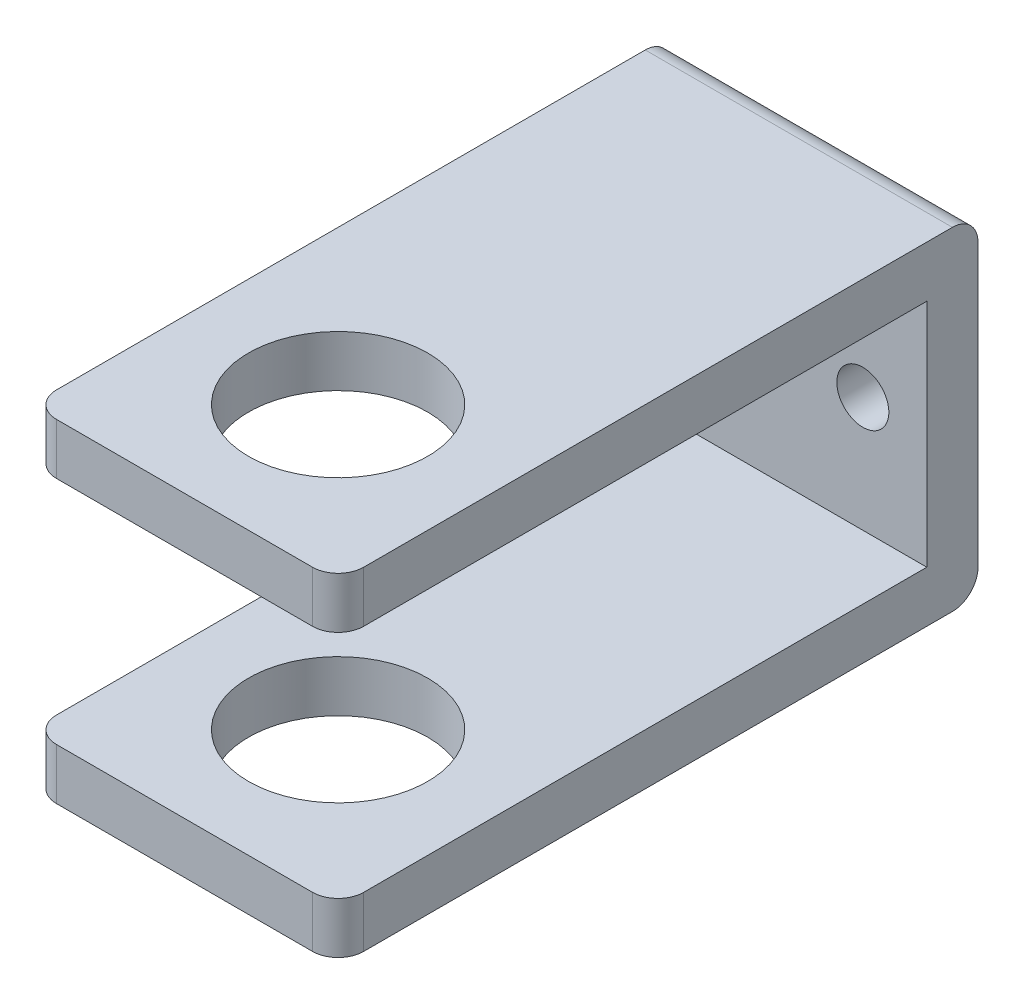
SolidWorks part; units mm, degrees
ref_plane "Front Plane" through (0, 0, 0) normal (0, 0, 1) x (1, 0, 0)
ref_plane "Top Plane" through (0, 0, 0) normal (0, 1, 0) x (1, 0, 0)
ref_plane "Right Plane" through (0, 0, 0) normal (1, 0, 0) x (0, 0, -1)
sketch "Sketch1" plane through (0, 0, 0) normal (0, 1, 0) x (1, 0, 0)
  line L1 (-19.05, -39.6875) -> (19.05, -39.6875)
  line L2 (-19.05, -39.6875) -> (-19.05, 39.6875)
  line L3 (-19.05, 39.6875) -> (19.05, 39.6875)
  line L4 (19.05, -39.6875) -> (19.05, 39.6875)
  line L5 (-19.05, -39.6875) -> (19.05, 39.6875) construction
  line L6 (-19.05, 39.6875) -> (19.05, -39.6875) construction
  point P0 (0, 0)
  dimension "D1" = 38.1
  dimension "D2" = 79.375
extrude "Boss-Extrude1" add sketch "Sketch1" along normal blind 41.275
sketch "Sketch2" plane through (0, 0, 39.6875) normal (0, 0, 1) x (1, 0, 0)
  line L0 (-19.05, 41.275) -> (-19.05, 0) construction
  line L1 (-19.05, 34.925) -> (19.05, 34.925)
  line L2 (-19.05, 34.925) -> (-19.05, 6.35)
  line L3 (-19.05, 6.35) -> (19.05, 6.35)
  line L4 (19.05, 34.925) -> (19.05, 6.35)
  line L5 (19.05, 41.275) -> (19.05, 0) construction
  line L6 (-19.05, 41.275) -> (19.05, 41.275) construction
  line L7 (-19.05, 0) -> (19.05, 0) construction
  dimension "D1" = 6.35
  dimension "D2" = 6.35
extrude "Cut-Extrude1" cut sketch "Sketch2" against normal offset from surface (73.025 mm away) 6.35 up to face at (0, 20.6375, -39.6875)
sketch "Sketch3" plane through (0, 41.275, 0) normal (0, 1, 0) x (1, 0, 0)
  line L1 (19.05, 39.6875) -> (-19.05, 39.6875) construction
  line L3 (2.7496, -15.875) -> (-2.7496, -15.875)
  line L4 (-2.7496, -15.875) -> (-5.4993, -20.6375)
  line L5 (-5.4993, -20.6375) -> (-2.7496, -25.4)
  line L6 (-2.7496, -25.4) -> (2.7496, -25.4)
  line L7 (2.7496, -25.4) -> (5.4993, -20.6375)
  line L8 (5.4993, -20.6375) -> (2.7496, -15.875)
  circle A0 centre (0, -20.6375) radius 50.8
  circle A1 centre (0, -20.6375) radius 4.7625 construction
  circle A2 centre (0, -20.6375) radius 11.1125
  dimension "D1" = 101.6
  dimension "D2" = 9.525
  dimension "D3" = 9.525
  dimension "D4" = 22.225
extrude "Cut-Extrude2" cut sketch "Sketch3" against normal through all contours L7 L8 L3 L4 L5 L6 | A2 L8 L7 L6 L5 L4 L3 region at (0, 41.275, 20.6375) region at (-10.7982, 41.275, 20.6375)
sketch "Sketch4" plane through (0, 0, -39.6875) normal (0, 0, -1) x (-1, 0, 0)
  line L0 (-19.05, 20.6375) -> (19.05, 20.6375) construction
  line L1 (-19.05, 41.275) -> (-19.05, 0) construction
  line L2 (19.05, 41.275) -> (19.05, 0) construction
  line L3 (11.1125, 20.6375) -> (-11.1125, 20.6375) construction
  circle A0 centre (11.1125, 20.6375) radius 3.2258
  circle A1 centre (-11.1125, 20.6375) radius 3.2258
  point P10 (0, 20.6375)
  point P11 (0, 0)
  point P12 (0, 20.6375)
  point P13 (-26.9451, 20.6375)
  dimension "D1" = 6.4516
  dimension "D2" = 22.225
extrude "Cut-Extrude3" cut sketch "Sketch4" against normal through all
fillet "Fillet2" radius 3.175 6 edges at (0, 0, -39.6875) (0, 41.275, -39.6875) (-19.05, 3.175, 39.6875) (19.05, 3.175, 39.6875) (-19.05, 38.1, 39.6875) (19.05, 38.1, 39.6875)
